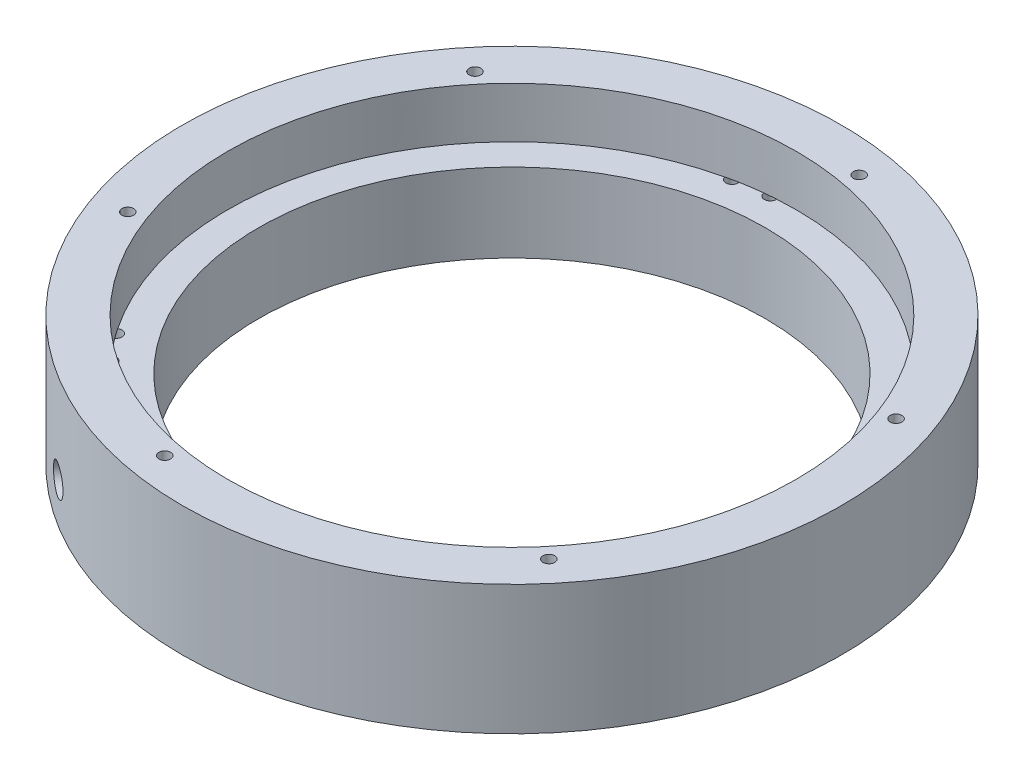
SolidWorks part; units mm, degrees
material "6061 Alloy"
ref_plane "Front Plane" through (0, 0, 0) normal (0, 0, 1) x (1, 0, 0)
ref_plane "Top Plane" through (0, 0, 0) normal (0, 1, 0) x (1, 0, 0)
ref_plane "Right Plane" through (0, 0, 0) normal (1, 0, 0) x (0, 0, -1)
sketch "Sketch1" plane through (0, 0, 0) normal (0, 1, 0) x (1, 0, 0)
  line L0 (26.7963, -63.1282) -> (0, 0) construction
  line L1 (0, 0) -> (0, -32.7983) construction
  line L2 (0, 0) -> (58.126, -27.1046) construction
  line L3 (0, 0) -> (-15.1655, -86.0079) construction
  line L4 (0, 0) -> (84.7676, -52.9687) construction
  circle A0 centre (0, 0) radius 57.15
  circle A1 centre (0, 0) radius 74.3712
  circle A3 centre (0, 0) radius 64.135
  circle A4 centre (-11.7434, -66.6001) radius 1.3208
  circle A5 centre (26.7963, -63.1282) radius 1.9939
  circle A6 centre (26.7963, -63.1282) radius 5.5626
  circle A7 centre (58.126, -27.1046) radius 1.3589
  circle A8 centre (60.9305, -20.0194) radius 1.3589
  dimension "D1" = 114.3
  dimension "D5" = 2.6416
  dimension "D7" = 3.9878
  dimension "D9" = 11.1252
  dimension "D10" = 2.7178
  dimension "D2" = 148.7424
  dimension "D4" = 67.6275
  dimension "D6" = 68.58
  dimension "D8" = 23
  dimension "D11" = 65
  dimension "D15" = 58
  dimension "D12" = 7.62
  dimension "D13" = 10
  dimension "D3" = 6.985
extrude "Boss-Extrude1" add sketch "Sketch1" along normal blind 17.78 contours A7 A3 A6 A0 | A3 A6 A5 | A5 | A3 A6 | A1 A7 A3 A6 A4 | A3 A7 | A3 A7 | A3 A8 | A3 A8 region at (-72.2677, 0, 0) region at (61.6385, 0, 9.1979) region at (24.877, 0, 58.6065) region at (25.1207, 0, 59.1805) region at (61.4759, 0, 20.1987) region at (60.3801, 0, 19.8386) region at (57.601, 0, 26.8598) region at (58.6464, 0, 27.3473) region at (26.7963, 0, 63.1282)
extrude "Boss-Extrude3" add sketch "Sketch1<3>" along normal blind 11.43 from surface contours A1 A7 A3 A6 A4 | A3 A6 A5 | A5 | A3 A7 | A3 A8 region at (-72.2677, 0, 0) region at (25.1207, 0, 59.1805) region at (61.4759, 0, 20.1987) region at (58.6464, 0, 27.3473) region at (26.7963, 0, 63.1282) starting at face at (0, 17.78, 57.15)
sketch "Sketch1<3>" plane through (0, 0, 0) normal (0, 1, 0) x (1, 0, 0) same geometry as "Sketch1"
pattern_circular "CirPattern1" count 6 over 360 about axis through (0, 29.21, 0) along (0, 1, 0) of face at (-11.7434, 0, 67.9209)
sketch "Sketch2" plane through (0, 0, 0) normal (1, 0, 0) x (0, 0, -1)
  line L0 (-57.15, 0) -> (57.15, 0) construction
  line L1 (57.15, 17.78) -> (-57.15, 17.78) construction
  line L2 (-57.15, 0) -> (57.15, 0)
  line L3 (57.15, 17.78) -> (-57.15, 17.78)
  line L4 (91.6697, 17.018) -> (97.1828, 17.018) construction
  line L5 (0, 17.78) -> (0, 35.8369)
  circle A0 centre (60.6425, 18.6055) radius 1.5875 construction
  circle A1 centre (60.6425, 18.669) radius 1.651
  dimension "D2" = 3.175
  dimension "D4" = 3.302
  dimension "D1" = 60.6425
  dimension "D3" = 0.762
extrude "Cut-Extrude2" cut sketch "Sketch1<4>" along normal blind 0.635 contours A3 A6 A5 | A3 A6 | A6 region at (24.877, 0, 58.6065) region at (25.1207, 0, 59.1805)
sketch "Sketch1<4>" plane through (0, 0, 0) normal (0, 1, 0) x (1, 0, 0) same geometry as "Sketch1"
extrude "Cut-Extrude3" cut sketch "Sketch1<5>" along normal blind 6.35 contours A5 region at (26.7963, 0, 63.1282)
sketch "Sketch1<5>" plane through (0, 0, 0) normal (0, 1, 0) x (1, 0, 0) same geometry as "Sketch1"
pattern_circular "CirPattern3" count 3 over 360 about axis through (0, 0, 0) along (0, 1, 0) of face at (26.7963, 6.35, 65.1221) of face at (26.7963, 6.35, 65.1221) of face at (26.7963, 0.635, 65.1221) of face at (26.7963, 0.635, 68.6908)
ref_plane "Plane1" through (0, 0, 0) normal (-0.5299, 0, 0.848) x (0.848, 0, 0.5299)
sketch "Sketch3" plane through (0, 0, 0) normal (-0.5299, 0, 0.848) x (0.848, 0, 0.5299)
  line L0 (57.15, 17.78) -> (-57.15, 17.78) construction
  line L1 (57.15, 17.78) -> (-57.15, 17.78)
  line L2 (0, 0) -> (0, 17.78) construction
  circle A0 centre (0, 8.89) radius 3.3528
  circle A1 centre (0, 8.89) radius 3.9751
  dimension "D1" = 6.7056
  dimension "D3" = 7.9502
  dimension "D2" = 8.89
extrude "Cut-Extrude5" cut sketch "Sketch3" along normal up to surface (74.2956 mm away) contours L2 A0 | A0 L2 region at (-1.2067, 8.89, -0.7541) region at (1.2067, 8.89, 0.7541) up to face at (0, 0, 74.3712)
extrude "Cut-Extrude13" cut sketch "Sketch1<6>" along normal up to surface (17.78 mm away) contours A3 A8 | A3 A8 | A7 region at (61.4759, 0, 20.1987) region at (60.3801, 0, 19.8386) up to face at (0, 17.78, 57.15)
sketch "Sketch1<6>" plane through (0, 0, 0) normal (0, 1, 0) x (1, 0, 0) same geometry as "Sketch1"
pattern_circular "CirPattern4" count 3 over 360 about axis through (0, 0, 0) along (0, 1, 0) of "Cut-Extrude13"
equation "\"Middle Coupler Inner Daimeter\"= 3.875in"
equation "\"Middle Coupler  Wall Thickness\" = 0.25in"
equation "\"Middle Coupler Bottom Thickness\"= 0.2in"
equation "\"Bearing Rail Offset\"= 0.45in"
equation "\"3-56 UNF Tap\"= 0.089in"
equation "\"3-56 UNF Clearance\"= 0.104in"
equation "\"Ball Bearing Distance\"= 0.03in"
equation "\"D1@Sketch1\"=\"Middle Coupler Inner Daimeter\"+0.625in"
equation "\"D3@Sketch1\"=0.275"
equation "\"D4@Sketch1\"=\"Middle Coupler Inner Daimeter\"/2+0.625/2+0.275+0.275/2"
equation "\"D5@Sketch1\"=\"3-48 Clearance\""
equation "\"D1@Sketch2\"=\"Middle Coupler Inner Daimeter\"/2in + \"Bearing Rail Offset\""
equation "\"D3@Sketch2\"=\"Ball Bearing Distance\""
equation "\"D4@Sketch2\"=\"D2@Sketch2\"+0.005"
equation "\"D1@Boss-Extrude3\"=0.320in+0.01in + 0.03*4"
equation "\"TCA Outer Diameter\" = 6in"
equation "\"Interstage Aeroframe Wall Thickness\" = 0.072in"
equation "\"Compression Spring OD\"= 0.42in"
equation "\"10-24 Tap\"= 0.157in"
equation "\"10-24 Clearance\"= 0.196in"
equation "\"Lower Stage Fuselage Wall Thickness\" = 0.25in"
equation "\"6-32 Tap\" = 0.107in"
equation "\"D10@Sketch1\"=\"6-32 Tap\""
equation "\"1/4-20 Tap\" = 0.201in"
equation "\"D1@Sketch3\"=0.254 + 0.01"
equation "\"12-24 Tap\" = 0.177in"
equation "\"D3@Sketch3\"=0.313"
equation "\"3-48 Tap\"= 0.079in"
equation "\"3-48 Clearance\" = 0.104in"
equation "\"6-32 Clearance\" = 0.144"
equation "\"D2@Sketch1\"=\"TCA Outer Diameter\"-\"Interstage Aeroframe Wall Thickness\"*2"
equation "\"D6@Sketch1\"=(\"Middle Coupler Inner Daimeter\"+\"TCA Outer Diameter\"+0.5+0.0125*2in)/4 + 0.1"
